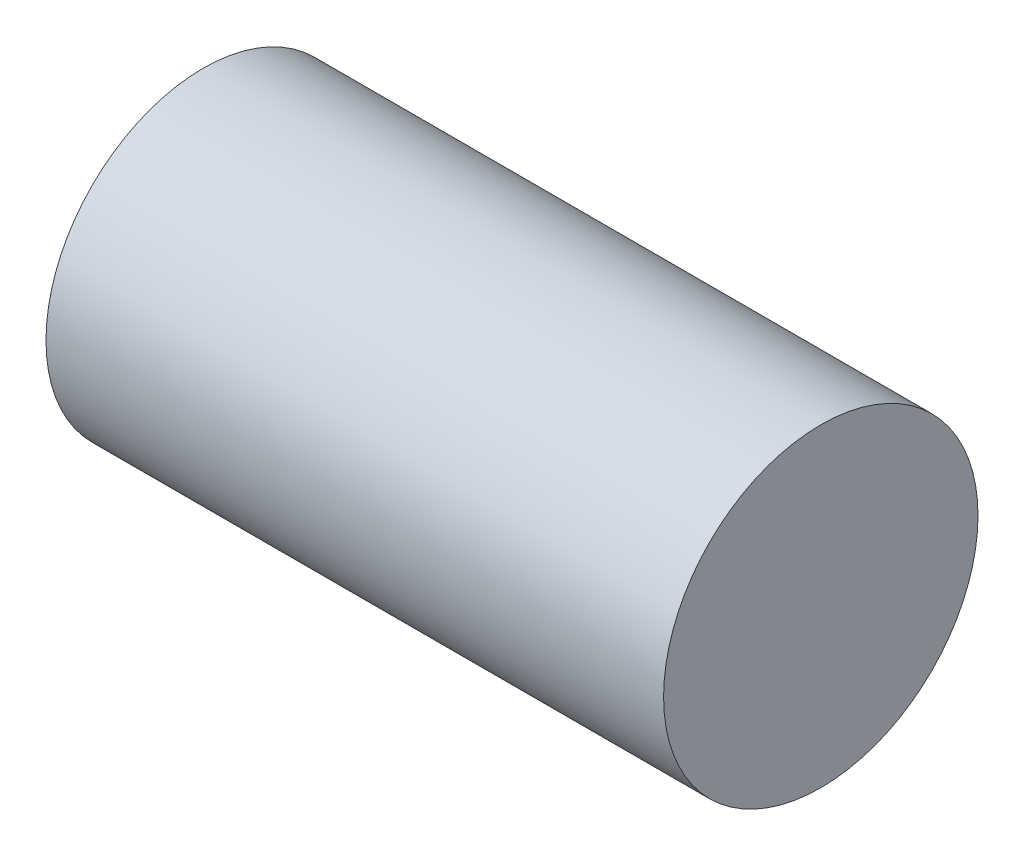
SolidWorks part; units mm, degrees
ref_plane "Front Plane" through (0, 0, 0) normal (0, 0, 1) x (1, 0, 0)
ref_plane "Top Plane" through (0, 0, 0) normal (0, 1, 0) x (1, 0, 0)
ref_plane "Right Plane" through (0, 0, 0) normal (1, 0, 0) x (0, 0, -1)
sketch "Hose_End_10 Sketch" plane through (0, 0, 0) normal (0, 0, 1) x (1, 0, 0)
  line L0 (-1000, 0) -> (1000, 0) construction
  line L1 (0, 0) -> (0, 14)
  line L2 (0, 14) -> (55, 14)
  line L3 (55, 14) -> (55, 0)
  line L4 (55, 0) -> (0, 0)
revolve "Hose_End_10" add sketch "Hose_End_10 Sketch" angle 360 about L0
ref_axis "Engine Axis" through (57.75, 0, 0) along (-1, 0, 0)
sketch "Socket 1 Sketch" plane through (0, 0, 0) normal (0, 0, 1) x (1, 0, 0)
  line L0 (-1000, 0) -> (1000, 0) construction
  line L1 (-1, 0) -> (-1, 6.35)
  line L2 (-1, 6.35) -> (22.9, 6.35)
  line L3 (22.9, 6.35) -> (22.9, 0)
  line L4 (22.9, 0) -> (-1, 0)
revolve "Socket 1" cut sketch "Socket 1 Sketch" angle 360 about L0
